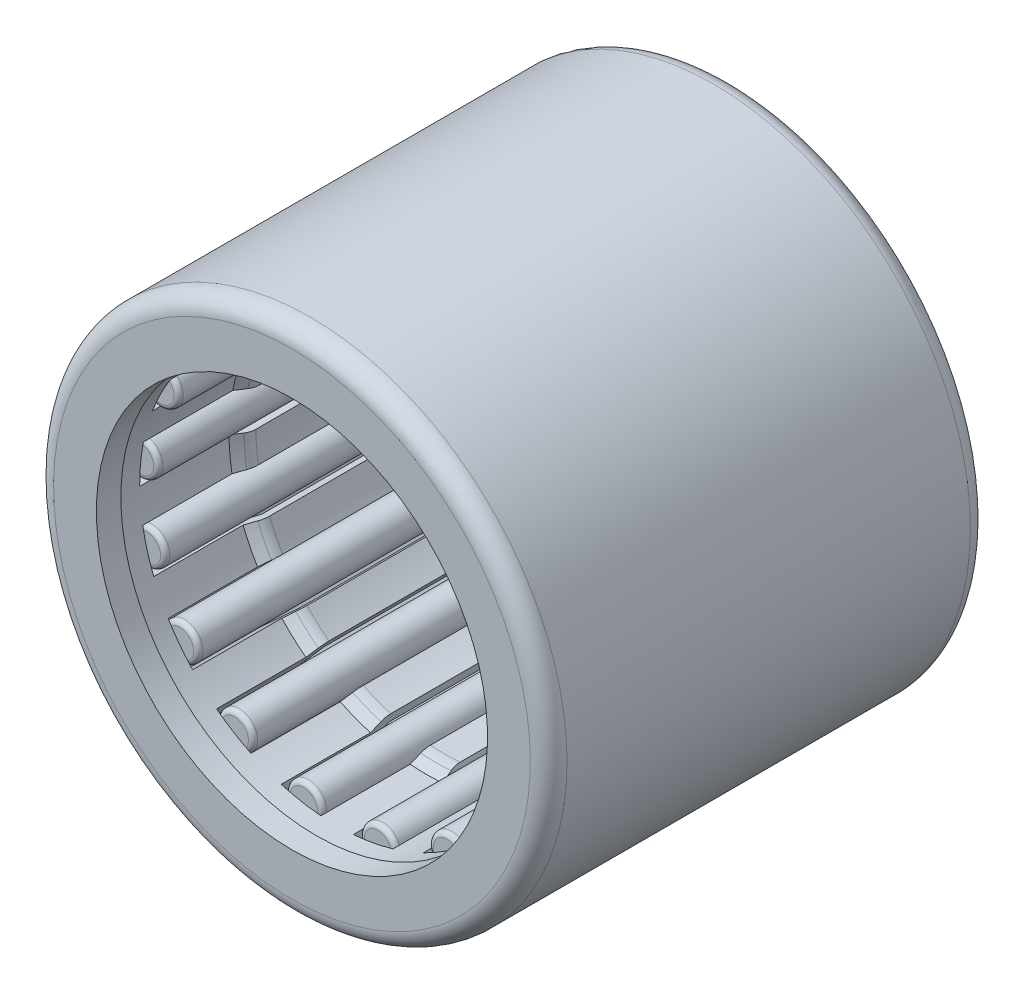
SolidWorks part; units mm, degrees
ref_plane "Front Plane" through (0, 0, 0) normal (0, 0, 1) x (1, 0, 0)
ref_plane "Top Plane" through (0, 0, 0) normal (0, 1, 0) x (1, 0, 0)
ref_plane "Right Plane" through (0, 0, 0) normal (1, 0, 0) x (0, 0, -1)
sketch "Sketch1" plane through (0, 0, 0) normal (1, 0, 0) x (0, 0, -1)
  line L0 (-6, 0) -> (6, 0) construction
  line L1 (6, 7) -> (-6, 7)
  line L2 (-6, -5) -> (-6, 5) construction
  line L3 (6, -7) -> (-6, -7) construction
  line L4 (-6, 7) -> (-6, 5.3333)
  line L5 (-6, 5.3333) -> (-5.3333, 5.3333)
  line L6 (-5.3333, 5.3333) -> (-5.3333, 6.3333)
  line L7 (-5.3333, 6.3333) -> (5.3333, 6.3333)
  line L8 (5.3333, 6.3333) -> (5.3333, 5.3333)
  line L9 (5.3333, 5.3333) -> (6, 5.3333)
  line L10 (6, 5.3333) -> (6, 7)
  line L11 (0, 0) -> (0, 5) construction
  line L12 (0, 5) -> (-6, 5) construction
  line L13 (0, 7) -> (0, 6.3333) construction
  line L14 (0, 6.3333) -> (0, 5.6667) construction
  line L15 (0, 5.6667) -> (0, 5) construction
  point P4 (0, 0)
  point P8 (0, 7)
  point P10 (-6, 0)
  point P24 (0, 5.3333)
  dimension "Width" = 12
  dimension "OD" = 14
  dimension "For Shaft Diameter" = 10
  dimension "ID" = 10
  dimension "For Housing ID" = 14
sketch "Sketch2" plane through (0, 0, 0) normal (1, 0, 0) x (0, 0, -1)
  line L8 (5.3333, 6.3333) -> (5.3333, 5.3333)
  line L9 (5.3333, 5.3333) -> (6, 5.3333)
  line L10 (6, 5.3333) -> (6, 7)
  line L11 (6, 7) -> (-6, 7)
  line L12 (-6, 7) -> (-6, 5.3333)
  line L13 (-6, 5.3333) -> (-5.3333, 5.3333)
  line L14 (-5.3333, 5.3333) -> (-5.3333, 6.3333)
  line L15 (-5.3333, 6.3333) -> (5.3333, 6.3333)
  line L16 (5.3333, 6.3333) -> (5.3333, 5.3333)
  line L17 (5.3333, 5.3333) -> (6, 5.3333)
  line L18 (6, 5.3333) -> (6, 7)
  line L19 (6, 7) -> (-6, 7)
  line L20 (-6, 7) -> (-6, 5.3333)
  line L21 (-6, 5.3333) -> (-5.3333, 5.3333)
  line L22 (-5.3333, 5.3333) -> (-5.3333, 6.3333)
  line L23 (-5.3333, 6.3333) -> (5.3333, 6.3333)
  dimension "D1" = 0
revolve "Revolve1" add sketch "Sketch2" angle 360 about L0
fillet "Fillet1" radius 0.5 2 edges at (0, -7, -6) (0, -7, 6)
sketch "Sketch4" plane through (0, 0, 0) normal (1, 0, 0) x (0, 0, -1)
  line L0 (0, 5) -> (0, 6) construction
  line L1 (0, 6.3333) -> (0, 5.6667) construction
  line L3 (-4.6667, 5) -> (4.6667, 5)
  line L4 (-4.6667, 5) -> (-4.6667, 5.5)
  line L5 (-4.6667, 5.5) -> (4.6667, 5.5)
  line L6 (4.6667, 5) -> (4.6667, 5.5)
  line L7 (0, 5.5) -> (0, 5) construction
  line L8 (-4.6667, 5.25) -> (4.6667, 5.25) construction
  line L9 (-5.3333, 5.3333) -> (-4.6667, 5.3333) construction
  line L10 (-6, 5.3333) -> (-5.3333, 5.3333) construction
  line L11 (0, 5) -> (-6, 5) construction
  point P5 (0, 5.25)
  point P16 (-4.7683, 5.3333)
  point P17 (4.7683, 5.3333)
  dimension "D1" = 0.1016
revolve "Revolve2" add sketch "Sketch4" angle 360 about L5
fillet "Fillet2" radius 0.127 2 edges at (0.5, 5.5, 4.6667) (0.5, 5.5, -4.6667)
sketch "Sketch8" plane through (0, 0, 0) normal (0, 0, 1) x (1, 0, 0)
  line L0 (0, 0) -> (0.5, 5.5) construction
  line L1 (0, -5) -> (0, 5) construction
  line L2 (0.5, 5.5) -> (-0.5, 5.5) construction
  line L3 (-0.5, 5.5) -> (0, 0) construction
  circle A0 centre (0, 5.5) radius 0.5
  circle A1 centre (0, 5.5) radius 0.5
  dimension "D1" = 10.389
pattern_circular "CirPattern2" count 17 over 360 about axis through (0, 0, 6) along (0, 0, -1) of bodies 105
sketch "Sketch5" plane through (0, 0, 0) normal (1, 0, 0) x (0, 0, -1)
  line L0 (5.3333, 6.3333) -> (5.3333, 5.3333) construction
  line L1 (-5.3333, 5.3841) -> (5.3333, 5.3841) construction
  line L2 (-5.3333, 5.3841) -> (-5.3333, 5.8333)
  line L3 (-5.3333, 5.8333) -> (5.3333, 5.8333) construction
  line L4 (5.3333, 5.3841) -> (5.3333, 5.8333)
  line L5 (-5.3333, 5.3841) -> (-2.3333, 5.3841)
  line L6 (-2.3333, 5.3841) -> (-1.9567, 5.1667)
  line L7 (-1.9567, 5.1667) -> (1.9567, 5.1667)
  line L8 (0, 0) -> (0, 5) construction
  line L9 (0, 0) -> (0, 5) construction
  line L11 (2.3333, 5.3841) -> (1.9567, 5.1667)
  line L12 (5.3333, 5.3841) -> (2.3333, 5.3841)
  line L13 (0, 5) -> (0, 5.3333) construction
  line L14 (-4.6667, 5) -> (0, 5) construction
  line L15 (-2.3333, 5) -> (-2.3333, 5.3841) construction
  line L16 (-5.3333, 5.8333) -> (-2.6092, 5.8333)
  line L17 (-2.6092, 5.8333) -> (-1.8311, 5.3841)
  line L18 (-1.8311, 5.3841) -> (1.8311, 5.3841)
  line L19 (1.8311, 5.3841) -> (2.6092, 5.8333)
  line L20 (2.6092, 5.8333) -> (5.3333, 5.8333)
  line L21 (-1.9567, 5.1667) -> (-1.8311, 5.3841) construction
  line L23 (-6, 5.3333) -> (-5.3333, 5.3333) construction
  point P10 (0, 5.1667)
  dimension "D1" = 30
  dimension "D2" = 0.0508
revolve "Revolve3" add sketch "Sketch5" angle 360 about L0
fillet "Fillet3" radius 0.508 2 edges at (0, -5.1667, 1.9567) (0, -5.1667, -1.9567)
sketch "Sketch6" plane through (0, 0, 0) normal (0, 0, 1) x (1, 0, 0)
  line L0 (0, 5) -> (0, 5.5) construction
  line L1 (0, 5) -> (0, 5.5) construction
  line L3 (-0.5508, 4.9492) -> (0.5508, 4.9492)
  line L4 (-0.5508, 4.9492) -> (-0.5508, 6.0508)
  line L5 (-0.5508, 6.0508) -> (0.5508, 6.0508)
  line L6 (0.5508, 4.9492) -> (0.5508, 6.0508)
  line L7 (0, 6.0508) -> (0, 4.9492) construction
  line L8 (-0.5508, 5.5) -> (0.5508, 5.5) construction
  circle A0 centre (0, 5.5) radius 0.5 construction
  circle A1 centre (0, 5.5) radius 0.5508 construction
  dimension "D1" = 0.0508
extrude "Cut-Extrude1" cut sketch "Sketch6" along normal up to vertex (4.7683 mm away) and the other way up to vertex (4.7683 mm away) up to point (0, 5.3333, 4.7683) other way up to point (0, 5.3333, -4.7683)
pattern_circular "CirPattern8" count 17 over 360 about axis through (0, 0, 6) along (0, 0, -1) of "Cut-Extrude1"
sketch "Sketch7" plane through (0, 0, 0) normal (0, 0, 1) x (1, 0, 0)
  circle A0 centre (0, 0) radius 5
  circle A1 centre (0, 0) radius 7
  point P3 (0, -5)
  point P5 (0, -7)
  point P8 (5, 0)
  point P11 (-7, 0)
  dimension "D1" = 10
equation "\"D1@Fillet1\"=(\"OD@Sketch1\"-\"For Shaft Diameter@Sketch1\")/8"
equation "\"D1@CirPattern2\"=360/\"D1@Sketch8\"/2"
equation "\"D2@Cut-Extrude1\"=\"D1@Cut-Extrude1\""
equation "\"D1@CirPattern8\"=\"D1@CirPattern2\""
